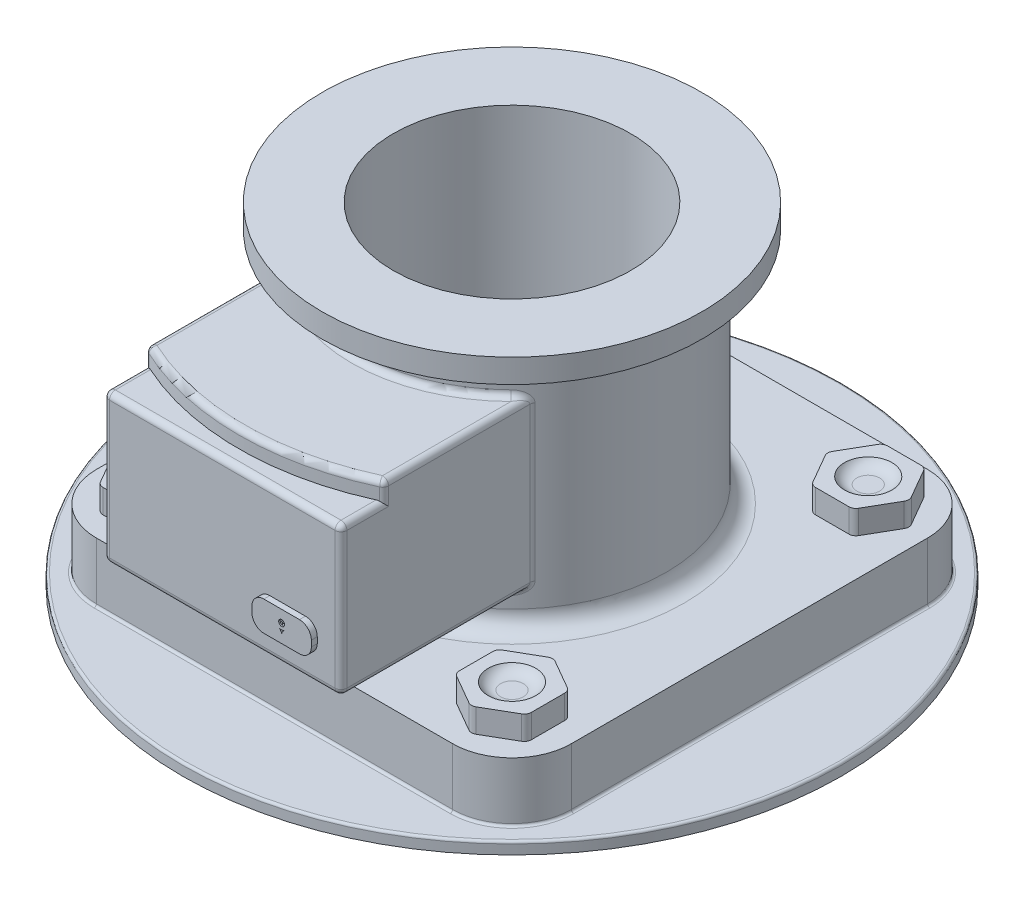
SolidWorks part; units mm, degrees
ref_plane "Front Plane" through (0, 0, 0) normal (0, 0, 1) x (1, 0, 0)
ref_plane "Top Plane" through (0, 0, 0) normal (0, 1, 0) x (1, 0, 0)
ref_plane "Right Plane" through (0, 0, 0) normal (1, 0, 0) x (0, 0, -1)
sketch "Sketch1" plane through (0, 0, 0) normal (0, 1, 0) x (1, 0, 0)
  circle A0 centre (0, 0) radius 277.5
  dimension "D1" = 555
extrude "Boss-Extrude1" add sketch "Sketch1" along normal blind 10
sketch "Sketch2" plane through (0, 10, 0) normal (0, 1, 0) x (1, 0, 0)
  line L1 (-200, -200) -> (200, -200)
  line L2 (-200, -200) -> (-200, 200)
  line L3 (-200, 200) -> (200, 200)
  line L4 (200, -200) -> (200, 200)
  line L5 (-200, -200) -> (200, 200) construction
  line L6 (-200, 200) -> (200, -200) construction
  point P0 (0, 0)
  dimension "D1" = 400
  dimension "D2" = 400
extrude "Boss-Extrude2" add sketch "Sketch2" along normal blind 50
fillet "Fillet1" radius 50 4 edges at (-200, 35, -200) (200, 35, -200) (200, 35, 200) (-200, 35, 200)
sketch "Sketch3" plane through (0, 60, 0) normal (0, 1, 0) x (1, 0, 0)
  circle A0 centre (0, 0) radius 130
  dimension "D1" = 260
extrude "Boss-Extrude3" add sketch "Sketch3" along normal blind 200
sketch "Sketch4" plane through (0, 260, 0) normal (0, 1, 0) x (1, 0, 0)
  circle A0 centre (0, 0) radius 160
  dimension "D1" = 320
extrude "Boss-Extrude4" add sketch "Sketch4" along normal blind 20
sketch "Sketch5" plane through (0, 0, 0) normal (0, 0, 1) x (1, 0, 0)
  line L0 (0, 0) -> (0, 160) construction
  line L1 (-150, 60) -> (150, 60) construction
  line L2 (-100, 230) -> (100, 230)
  line L3 (-100, 230) -> (-100, 90)
  line L4 (-100, 90) -> (100, 90)
  line L5 (100, 230) -> (100, 90)
  line L6 (-100, 230) -> (100, 90) construction
  line L7 (-100, 90) -> (100, 230) construction
  dimension "D1" = 200
  dimension "D2" = 140
  dimension "D3" = 30
extrude "Boss-Extrude5" add sketch "Sketch5" along normal blind 244
sketch "Sketch6" plane through (0, 230, 0) normal (0, 1, 0) x (1, 0, 0)
  circle A0 centre (0, 0) radius 230
  dimension "D1" = 460
extrude "Cut-Extrude1" cut sketch "Sketch6" against normal blind 15 flip side to cut
sketch "Sketch7" plane through (0, 280, 0) normal (0, 1, 0) x (1, 0, 0)
  circle A0 centre (0, 0) radius 100
  circle A1 centre (0, 0) radius 160 construction
  dimension "D1" = 200
extrude "Cut-Extrude2" cut sketch "Sketch7" against normal blind 200
fillet "Fillet2" radius 5 17 edges at (0, 90, 130) (-100, 90, 163.5331) (-100, 160, 83.0662) (-100, 222.5, 207.1232) (-100, 215, 225.5616) (0, 90, 244) (-100, 152.5, 244) (0, 215, 244) (100, 222.5, 207.1232) (100, 160, 83.0662) (100, 90, 163.5331) (100, 152.5, 244) (100, 215, 225.5616) (-100, 230, 145.0947) (0, 230, 130) (100, 230, 145.0947) (0, 230, 230)
fillet "Fillet3" radius 15 1 edges at (0, 60, 130)
fillet "Fillet4" radius 2 9 edges at (-185.3553, 10, 185.3553) (0, 10, 200) (185.3553, 10, 185.3553) (200, 10, 0) (185.3553, 10, -185.3553) (0, 10, -200) (-185.3553, 10, -185.3553) (-200, 10, 0) (0, 10, 277.5)
sketch "Sketch8" plane through (0, 60, 0) normal (0, 1, 0) x (1, 0, 0)
  line L1 (180.3109, -132.5) -> (150, -115)
  line L2 (150, -115) -> (119.6891, -132.5)
  line L3 (119.6891, -132.5) -> (119.6891, -167.5)
  line L4 (119.6891, -167.5) -> (150, -185)
  line L5 (150, -185) -> (180.3109, -167.5)
  line L6 (180.3109, -167.5) -> (180.3109, -132.5)
  circle A0 centre (150, -150) radius 30.3109 construction
  dimension "D1" = 35
extrude "Boss-Extrude6" add sketch "Sketch8" along normal blind 20
sketch "Sketch9" plane through (0, 80, 0) normal (0, 1, 0) x (1, 0, 0)
  line L0 (119.6891, -167.5) -> (180.3109, -132.5) construction
  circle A0 centre (150, -150) radius 20
  point P6 (0, 0)
  dimension "D1" = 40
extrude "Cut-Extrude3" cut sketch "Sketch9" against normal blind 6
fillet "Fillet5" radius 6 6 edges at (119.6891, 70, 132.5) (150, 70, 115) (119.6891, 70, 167.5) (180.3109, 70, 132.5) (180.3109, 70, 167.5) (150, 70, 185)
fillet "Fillet6" radius 12 1 edges at (150, 74, 170)
pattern_circular "CirPattern2" count 4 over 360 about axis through (0, 80, 0) along (0, 1, 0) of "Boss-Extrude6", "Fillet5" reverse direction yes
pattern_circular "CirPattern4" count 4 over 360 about axis through (0, 260, 0) along (0, -1, 0) of "Fillet6", "Cut-Extrude3" reverse direction yes
sketch "Sketch10" plane through (0, 0, 244) normal (0, 0, 1) x (1, 0, 0)
  line L0 (95, 95) -> (95, 210) construction
  line L1 (30, 135) -> (80, 135)
  line L2 (30, 135) -> (30, 110)
  line L3 (30, 110) -> (80, 110)
  line L4 (80, 135) -> (80, 110)
  line L5 (-95, 95) -> (95, 95) construction
  dimension "D1" = 15
  dimension "D2" = 15
  dimension "D3" = 50
  dimension "D4" = 25
extrude "Boss-Extrude7" add sketch "Sketch10" along normal blind 5
fillet "Fillet7" radius 10 4 edges at (30, 135, 246.5) (30, 110, 246.5) (80, 110, 246.5) (80, 135, 246.5)
sketch "Sketch11" plane through (0, 0, 249) normal (0, 0, 1) x (1, 0, 0)
  line L0 (55, 135) -> (55, 125) construction
  line L1 (70, 135) -> (40, 135) construction
  circle A0 centre (55, 125) radius 1
  circle A1 centre (55, 125) radius 2.5
  circle A2 centre (55, 125) radius 5
  circle A3 centre (50, 116.3397) radius 5
  circle A4 centre (60, 116.3397) radius 5
  dimension "D1" = 10
  dimension "D2" = 5
  dimension "D3" = 2
  dimension "D4" = 10
extrude "Cut-Extrude4" cut sketch "Sketch11" against normal blind 10 contours A3 A4 A2 region at (55, 119.2265, 249)
extrude "Cut-Extrude5" cut sketch "Sketch11<3>" against normal blind 2 contours A1 A0 region at (52.5707, 125, 249)
sketch "Sketch11<3>" plane through (0, 0, 249) normal (0, 0, 1) x (1, 0, 0) same geometry as "Sketch11"
fillet "Fillet8" radius 1 1 edges at (57.5, 125, 247)
chamfer "Chamfer1" distance 0.1 angle 45 1 edges at (56, 125, 249)
